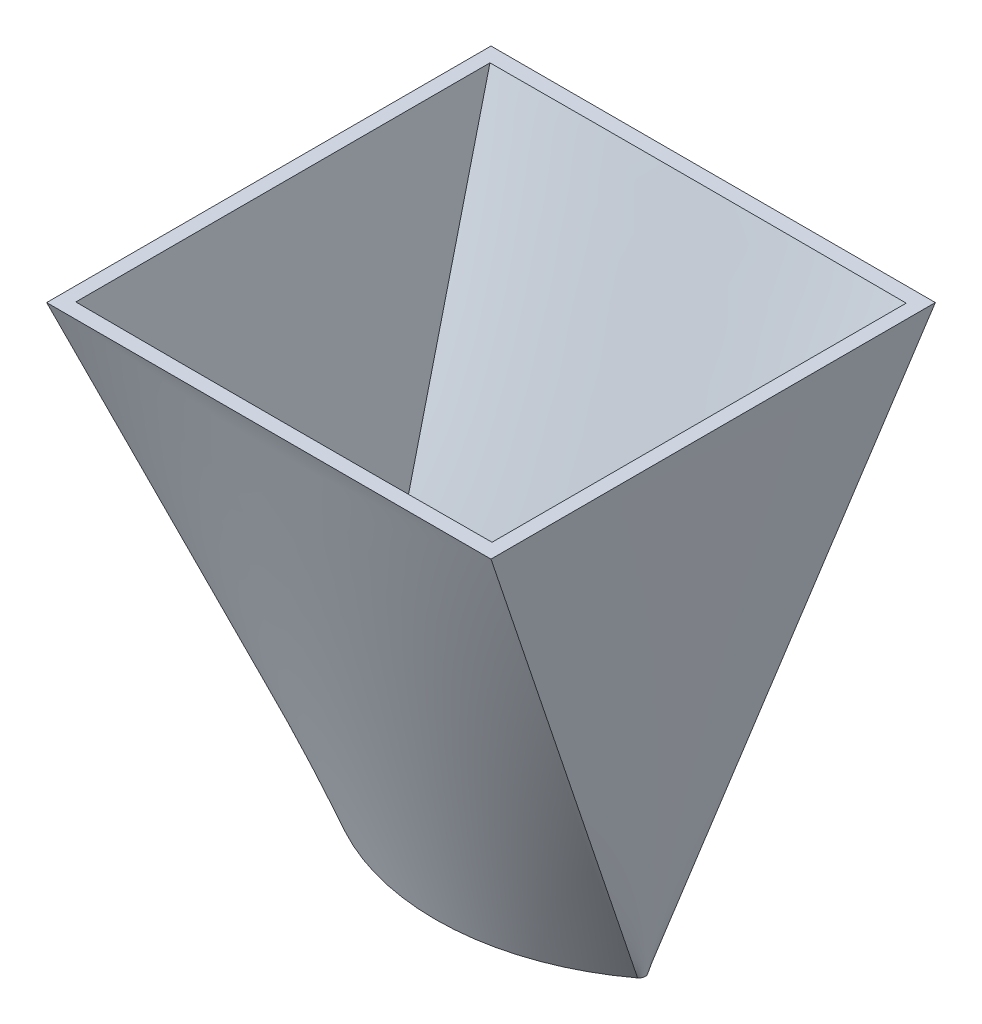
SolidWorks part; units mm, degrees
ref_plane "Alzado" through (0, 0, 0) normal (0, 0, 1) x (1, 0, 0)
ref_plane "Planta" through (0, 0, 0) normal (0, 1, 0) x (1, 0, 0)
ref_plane "Vista lateral" through (0, 0, 0) normal (1, 0, 0) x (0, 0, -1)
sketch "Croquis1" plane through (0, 0, 0) normal (0, 1, 0) x (1, 0, 0)
  arc A0 (-23.957, -0.8008) -> (-23.957, 0.8008) centre (-23.3581, 0) cw
  arc A1 (-23.957, 0.8008) -> (23.957, 0.8008) centre (0, -31.2314) cw
  arc A2 (23.957, 0.8008) -> (23.957, -0.8008) centre (23.3581, 0) cw
  arc A3 (23.957, -0.8008) -> (-23.957, -0.8008) centre (0, 31.2314) cw
  point P8 (-9.6252, 1.3993)
  point P9 (0, 0)
  point P11 (0, 0)
  point P12 (0, 8.7686)
  dimension "D1" = 1
  dimension "D2" = 40
  dimension "D3" = 47.914
ref_plane "Plano1" through (0, 80, 0) normal (0, 1, 0) x (1, 0, 0)
sketch3d "Croquis3D2"
  line L0 (-35.0893, 80, 35.0893) -> (-25.457, 0, 2.4178) construction
  line L1 (-35.0893, 80, -35.0893) -> (-35.0893, 80, 35.0893)
  line L2 (-35.0893, 80, -35.0893) -> (35.0893, 80, -35.0893)
  line L3 (35.0893, 80, -35.0893) -> (35.0893, 80, 35.0893)
  line L4 (-35.0893, 80, 35.0893) -> (35.0893, 80, 35.0893)
  line L5 (-35.0893, 80, -35.0893) -> (35.0893, 80, 35.0893) construction
  line L6 (35.0893, 80, -35.0893) -> (-35.0893, 80, 35.0893) construction
  line L7 (-35.0893, 80, 0) -> (-26.6809, 0, 0) construction
  line L8 (-26.6809, 0, 0) -> (-26.6809, 9.4179, 0) construction
  arc A0 (-25.457, 0, 2.4178) -> (-25.457, 0, -2.4178) centre (-23.6809, 0, 0) ccw construction
  point P0 (0, 80, 0)
  point P13 (-23.6809, -3, 0)
  dimension "D1" = 6
loft "Recubrir1" add profiles "Croquis1", "Croquis3D2" connector at (23.957, 0, -0.8008) connector at (35.0893, 80, -35.0893)
shell "Vaciado1" thickness 2.2 removed face at (0, 0, 0) removed face at (0, 80, 0)
fillet "Redondeo1" radius 1 2 edges at (0, 0, 6.4526) (0, 0, -6.4526)
